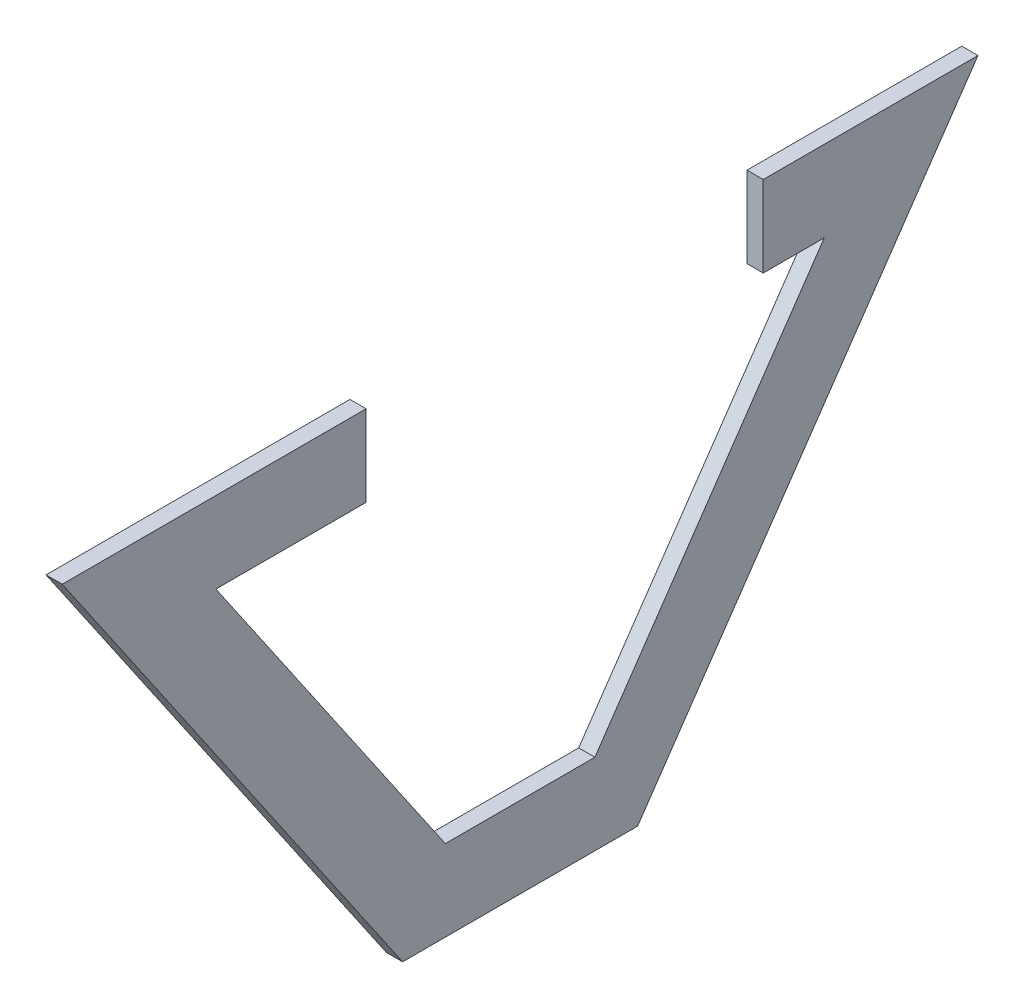
SolidWorks part; units mm, degrees
ref_plane "Front Plane" through (0, 0, 0) normal (0, 0, 1) x (1, 0, 0)
ref_plane "Top Plane" through (0, 0, 0) normal (0, 1, 0) x (1, 0, 0)
ref_plane "Right Plane" through (0, 0, 0) normal (1, 0, 0) x (0, 0, -1)
sketch "Sketch1" plane through (0, 0, 0) normal (1, 0, 0) x (0, 0, -1)
  line L0 (0, 24.4397) -> (0, -31.8822) construction
  line L1 (-14.5, -22.0259) -> (14.5, -22.0259)
  line L2 (14.5, -22.0259) -> (56.5, 39.3247)
  line L3 (56.5, 39.3247) -> (-56.5, 39.3247)
  line L4 (-9.2271, -12.0259) -> (9.2271, -12.0259)
  line L5 (9.2271, -12.0259) -> (37.5353, 29.3247)
  line L6 (37.5353, 29.3247) -> (-37.5353, 29.3247)
  line L7 (-9.2271, -12.0259) -> (-37.5353, 29.3247)
  line L8 (-14.5, -22.0259) -> (-56.5, 39.3247)
  point P13 (0, 29.3247)
  point P14 (0, -12.0259)
  point P15 (0, 39.3247)
  point P16 (0, -22.0259)
  dimension "D1" = 14.5
  dimension "D2" = 56.5
  dimension "D3" = 10
  dimension "D4" = 10
  dimension "D5" = 10
base flange "Base-Flange1" sketch "Sketch1" thickness 2 reverse thickness direction no parameters "D1"=10
sketch "Sketch6" plane through (0, 0, 0) normal (1, 0, 0) x (0, 0, -1)
  line L0 (-19, 45.7274) -> (-19, 29.0921)
  line L1 (-19, 29.0921) -> (30, 29.0921)
  line L2 (30, 29.0921) -> (30, 45.7274)
  line L3 (30, 45.7274) -> (-19, 45.7274)
  dimension "D1" = 49
  dimension "D2" = 19
extrude "Cut-Extrude1" cut sketch "Sketch6" against normal blind 49 normal cut yes
sketch "Bend-Lines1" [suppressed] plane through (0, 0, 0) normal (0, 1, 0) x (1, 0, 0)
sketch "Bounding-Box1" [suppressed] plane through (0, 0, 0) normal (0, 1, 0) x (1, 0, 0)
sheet metal parameters "Sheet-Metal1" thickness 2 parameters "D1"=10
flat pattern "Flat-Pattern1" [suppressed]
sketch "Bend-Lines2" plane through (0, 0, 0) normal (0, 1, 0) x (1, 0, 0)
sketch3d "Bounding-Box2" [suppressed]
  line L0 (64.15, -22.0259, 0) -> (-64.15, -22.0259, 0) construction
  line L1 (64.15, 39.3247, 0) -> (-64.15, 39.3247, 0) construction
  line L2 (64.15, -22.0259, 0) -> (64.15, 39.3247, 0) construction
  line L3 (-64.15, -22.0259, 0) -> (-64.15, 39.3247, 0) construction
sheet metal parameters "Sheet-Metal2" thickness 2 parameters "D1"=10
flat pattern "Flat-Pattern1"
sketch "Bend-Lines2" plane through (0, 0, 0) normal (0, 1, 0) x (1, 0, 0)
sketch3d "Bounding-Box2" [suppressed]
  line L0 (-56.5, -22.0259, 0) -> (56.5, -22.0259, 0) construction
  line L1 (-56.5, 39.3247, 0) -> (56.5, 39.3247, 0) construction
  line L2 (-56.5, -22.0259, 0) -> (-56.5, 39.3247, 0) construction
  line L3 (56.5, -22.0259, 0) -> (56.5, 39.3247, 0) construction
